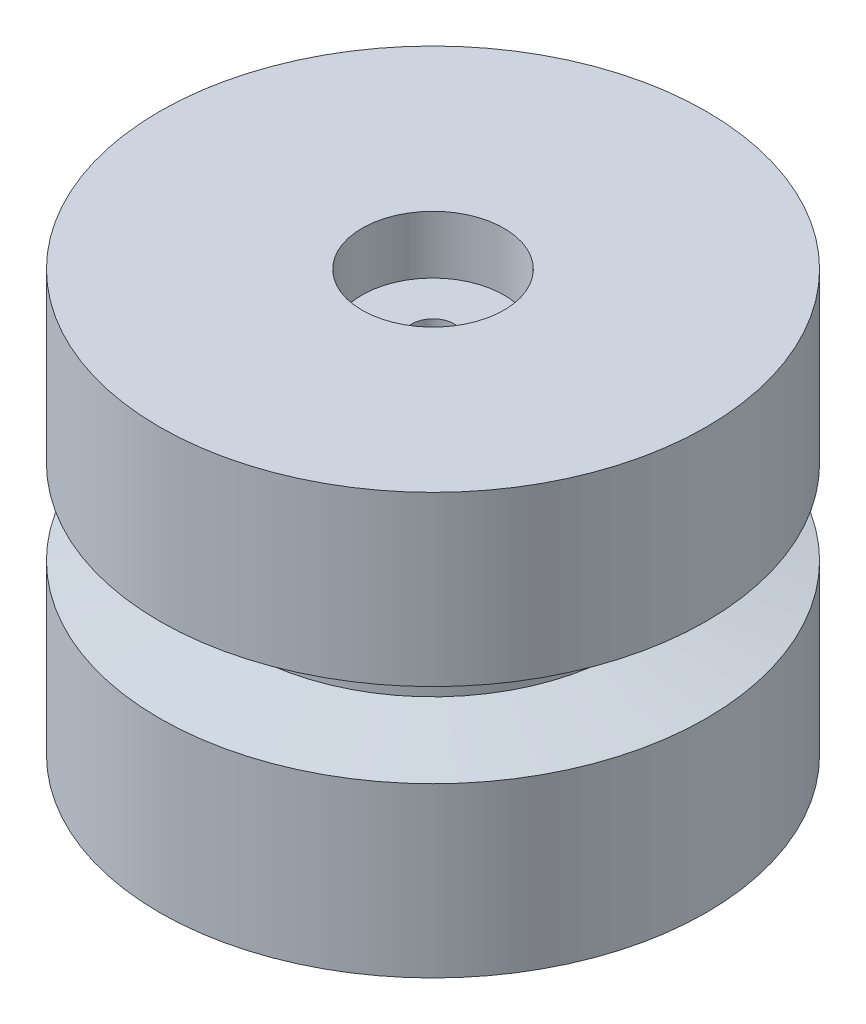
SolidWorks part; units mm, degrees
material "ABS"
ref_plane "Front" through (0, 0, 0) normal (0, 0, 1) x (1, 0, 0)
ref_plane "Top" through (0, 0, 0) normal (0, 1, 0) x (1, 0, 0)
ref_plane "Right" through (0, 0, 0) normal (1, 0, 0) x (0, 0, -1)
sketch "Sketch1" plane through (0, 0, 0) normal (0, 1, 0) x (1, 0, 0)
  circle A0 centre (0, 0) radius 26
  dimension "D1" = 52
extrude "Boss-Extrude1" add sketch "Sketch1" along normal blind 40
sketch "Sketch2" plane through (0, 0, 0) normal (0, -1, 0) x (1, 0, 0)
  circle A0 centre (0, 0) radius 11.25
  dimension "D1" = 22.5
extrude "608_Bearing_Hole" cut sketch "Sketch2" against normal blind 7.5
sketch "Sketch3" plane through (0, 40, 0) normal (0, 1, 0) x (1, 0, 0)
  circle A0 centre (0, 0) radius 6.75
  dimension "D1" = 13.5
extrude "624_Bearing_Hole" cut sketch "Sketch3" against normal blind 5.5
sketch "Sketch4" plane through (0, 40, 0) normal (0, 1, 0) x (1, 0, 0)
  circle A0 centre (0, 0) radius 2
  dimension "D1" = 4
extrude "Cut-Extrude3" cut sketch "Sketch4" against normal through all
sketch "Sketch5" plane through (0, 0, 0) normal (1, 0, 0) x (0, 0, -1)
  line L0 (26, 0) -> (26, 40) construction
  line L1 (26, 0) -> (26, 40)
  line L2 (26, 20) -> (-26, 20) construction
  line L3 (-26, 40) -> (-26, 0) construction
  line L4 (-18, 17.5) -> (-18, 22.5)
  line L5 (-26, 16) -> (-26, 24)
  line L6 (-26, 40) -> (-26, 0) construction
  line L7 (-26, 40) -> (-26, 0) construction
  line L8 (-26, 24) -> (-18, 22.5)
  line L9 (-26, 16) -> (-18, 17.5)
  line L10 (0, 0) -> (0, 40) construction
  line L11 (6.75, 40) -> (-6.75, 40) construction
  point P9 (-18, 20)
  point P14 (-26, 20)
  dimension "D1" = 5
  dimension "D2" = 8
  dimension "D3" = 8
ref_axis "Axis1" through (0, 40, 0) along (0, -1, 0)
revolve "Cut-Revolve1" cut sketch "Sketch5" angle 360 about L10 region at (0, 20, 22.3077)
